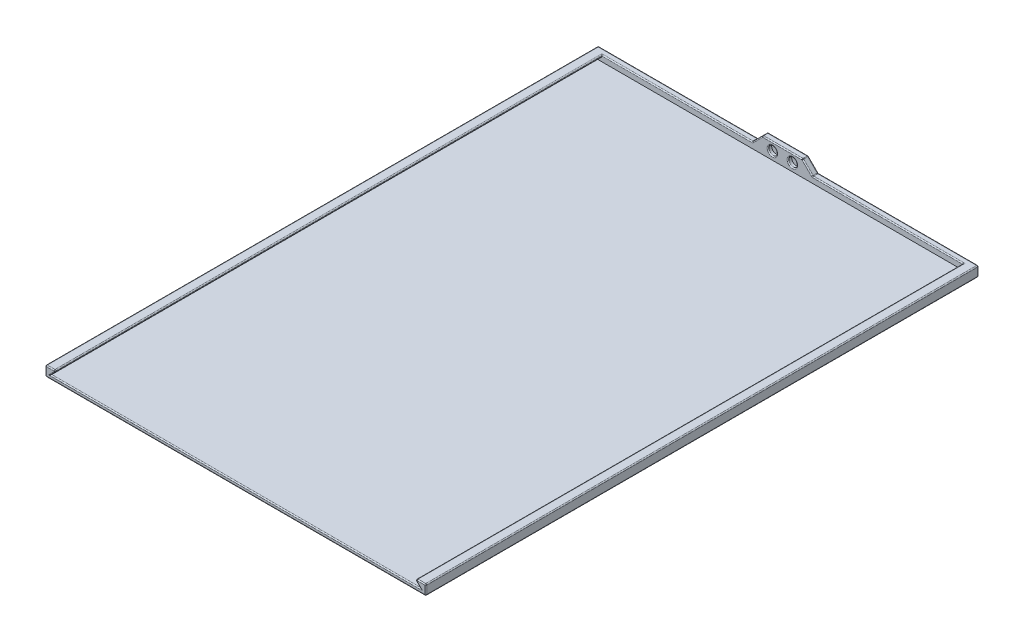
SolidWorks part; units mm, degrees
note: The reader was unsure of these and kept them because the rebuilt part matched: shared geometry of "Sketch1<3>", "Sketch1<5>".
ref_plane "Front Plane" through (0, 0, 0) normal (0, 0, 1) x (1, 0, 0)
ref_plane "Top Plane" through (0, 0, 0) normal (0, 1, 0) x (1, 0, 0)
ref_plane "Right Plane" through (0, 0, 0) normal (1, 0, 0) x (0, 0, -1)
sketch "Sketch1" plane through (0, 0, 0) normal (0, 0, 1) x (1, 0, 0)
  line L1 (0, 3) -> (4.8, 3)
  line L4 (3, 0) -> (95, 0)
  line L5 (95, -2) -> (0, -2)
  line L7 (95, -2) -> (95, 0)
  line L8 (0, -2) -> (0, 3)
  line L9 (5, 3) -> (5, 2) construction
  line L10 (5, 2) -> (3, 0) construction
  line L11 (3, 0) -> (0, 0) construction
  line L12 (5, 2) -> (5, 0) construction
  line L13 (4.8, 3) -> (4.8, 2.0828)
  line L14 (4.8, 2.0828) -> (2.8586, 0.1414)
  line L15 (2.8586, 0.1414) -> (2.7172, 0)
  line L16 (2.7172, 0) -> (3, 0)
  line L17 (4.8, 3) -> (5, 3) construction
  line L18 (4.8, 3) -> (80, 3)
  line L19 (95, 3) -> (95, 0)
  line L20 (80, 3) -> (85, 8)
  line L21 (85, 8) -> (95, 8)
  line L22 (95, 8) -> (95, 3)
  line L23 (80, 3) -> (95, 3) construction
  line L24 (90, 8) -> (90, 0) construction
  circle A1 centre (90, 4) radius 2.15
  dimension "D11" = 4.3
  dimension "D1" = 2
  dimension "D2" = 5
  dimension "D3" = 3
  dimension "D4" = 5
  dimension "D5" = 1
  dimension "D6" = 2
  dimension "D8" = 95
  dimension "D9" = 5
  dimension "D10" = 10
  dimension "D7" = 0.2
extrude "Boss-Extrude1" add sketch "Sketch1" along normal blind 273.15 contours L16 L15 L14 L13 L1 L8 L5 L7 L4
extrude "Boss-Extrude2" add sketch "Sketch1<3>" against normal blind 3 contours L16 L15 L14 L13 L1 L8 L5 L7 L4 | A1 | L22 L21 L20 L18 L13 L14 L15 L16 L4 L19 A1
sketch "Sketch1<3>" plane through (0, 0, 0) normal (0, 0, 1) x (1, 0, 0) same geometry as "Sketch1"
extrude "Cut-Extrude1" cut sketch "Sketch1<5>" against normal blind 1.8 contours A1
sketch "Sketch1<5>" plane through (0, 0, 0) normal (0, 0, 1) x (1, 0, 0) same geometry as "Sketch1"
mirror "Mirror1" about plane through (95, 0, 273.15) normal (-1, 0, 0) of bodies 107 104
fillet "Fillet1" radius 0.5 37 edges at (3.7586, 1.0414, 273.15) (0, -2, 135.075) (0, 3, 135.075) (4.8, 3, 136.575) (4.8, 2.0828, 136.575) (4.8, 2.5414, 273.15) (2.4, 3, 273.15) (42.4, 3, 0) (0, 0.5, 273.15) (82.5, 5.5, 0) (80, 3, -1.5) (95, 8, 0) (85, 8, -1.5) (95, -2, -3) (0, 0.5, -3) (40, 3, -3) (82.5, 5.5, -3) (95, 8, -3) (95, -2, 273.15) (92.15, 4, 0) (185.2, 2.0828, 136.575) (185.2, 3, 136.575) (190, 3, 135.075) (150, 3, -3) (110, 3, -1.5) (190, -2, 135.075) (190, 0.5, -3) (95, 0, 273.15) (190, 0.5, 273.15) (187.6, 3, 273.15) (185.2, 2.5414, 273.15) (186.2414, 1.0414, 273.15) (107.5, 5.5, -3) (105, 8, -1.5) (97.85, 4, 0) (147.6, 3, 0) (107.5, 5.5, 0)
